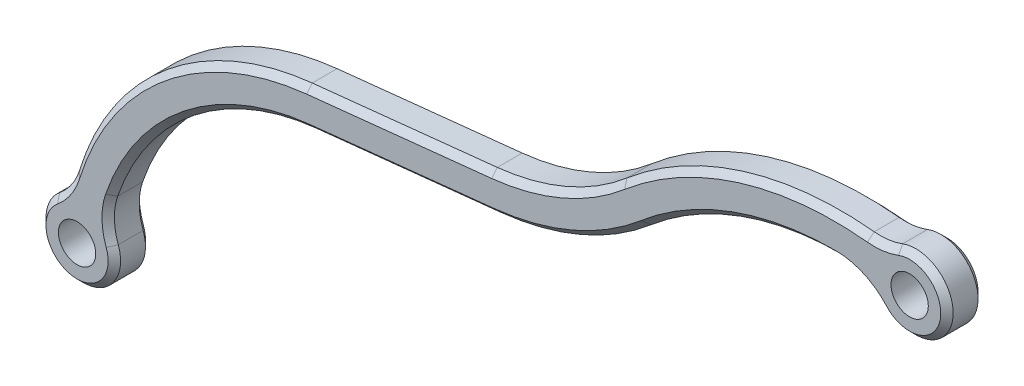
SolidWorks part; units mm, degrees
ref_plane "Спереди" through (0, 0, 0) normal (0, 0, 1) x (1, 0, 0)
ref_plane "Сверху" through (0, 0, 0) normal (0, 1, 0) x (1, 0, 0)
ref_plane "Справа" through (0, 0, 0) normal (1, 0, 0) x (0, 0, -1)
other "Configuration Table"
sketch "Sketch1" plane through (0, 0, 0) normal (0, 0, 1) x (1, 0, 0)
  line L0 (-54.4883, 1.7083) -> (-63.9363, 0.7152) construction
  line L1 (-54.4883, 1.7083) -> (-63.9363, 0.7152) construction
  line L2 (-65.383, -1.297) -> (-50.4992, 0.2674)
  circle A0 centre (-83.9505, -19.9121) radius 1.5 construction
  circle A1 centre (-83.9505, -19.9121) radius 1.5
  circle A2 centre (-17, 9.9282) radius 1.5 construction
  circle A3 centre (-17, 9.9282) radius 1.5
  circle A4 centre (-83.9505, -19.9121) radius 3
  circle A5 centre (-17, 9.9282) radius 3
  arc A6 (-12.8452, 4.492) -> (-12.8452, 1.508) centre (-13, 3) ccw construction
  arc A7 (-12.8452, 4.492) -> (-12.8452, 1.508) centre (-13, 3) ccw construction
  arc A9 (-83.3396, -17.8158) -> (-65.383, -1.297) centre (-63.2448, -21.6405) cw
  arc A10 (-50.4992, 0.2674) -> (-39.2623, 5.0886) centre (-52.6577, 20.804) ccw
  arc A11 (-39.2623, 5.0886) -> (-19.139, 10.7644) centre (-23.0284, -13.9569) cw
  dimension "D1" = 6
  dimension "D2" = 6
extrude "Boss-Extrude1" add sketch "Sketch1" along normal blind 3 contours A4 A1 | A5 A3 region at (-16.5387, 12.8066, 0) region at (-81.6367, -18.1389, 0)
sketch "Sketch2" plane through (0, 0, 0) normal (0, 0, 1) x (1, 0, 0)
  line L0 (-65.383, -1.297) -> (-50.4992, 0.2674) construction
  line L1 (-65.383, -1.297) -> (-50.4992, 0.2674)
  arc A0 (-19.139, 10.7644) -> (-39.2623, 5.0886) centre (-23.0284, -13.9569) ccw construction
  arc A1 (-50.4992, 0.2674) -> (-39.2623, 5.0886) centre (-52.6577, 20.804) ccw construction
  arc A2 (-65.383, -1.297) -> (-83.3396, -17.8158) centre (-63.2448, -21.6405) ccw construction
  arc A3 (-18.8959, 10.7249) -> (-39.2623, 5.0886) centre (-23.0284, -13.9569) ccw
  arc A4 (-50.4992, 0.2674) -> (-39.2623, 5.0886) centre (-52.6577, 20.804) ccw
  arc A5 (-65.383, -1.297) -> (-83.3396, -17.8158) centre (-63.2448, -21.6405) ccw
extrude "Extrude-Thin1" add sketch "Sketch2" along normal blind 3 thin thin type mid plane wall 3
fillet "Fillet1" radius 5 4 edges at (-84.7063, -17.0089, 1.5) (-81.8095, -17.8108, 1.5) (-19.9468, 9.3658, 1.5) (-18.9047, 12.246, 1.5)
chamfer "Chamfer1" distance 0.5 angle 45 28 edges at (-31.1067, 8.138, 0) (-43.9243, 0.4487, 0) (-57.7843, -2.0066, 0) (-75.0623, -6.8195, 0) (-30.9252, 11.3657, 0) (-81.4502, -17.1934, 0) (-45.1071, 3.2057, 0) (-84.7375, -22.8071, 0) (-58.0979, 0.977, 0) (-84.8606, -16.5059, 0) (-77.1954, -4.6867, 0) (-31.1067, 8.138, 3) (-43.9243, 0.4487, 3) (-57.7843, -2.0066, 3) (-75.0623, -6.8195, 3) (-30.9252, 11.3657, 3) (-81.4502, -17.1934, 3) (-45.1071, 3.2057, 3) (-84.7375, -22.8071, 3) (-58.0979, 0.977, 3) (-84.8606, -16.5059, 3) (-77.1954, -4.6867, 3) (-20.8969, 9.1322, 0) (-14.0837, 9.2244, 0) (-19.1882, 12.4496, 0) (-20.8969, 9.1322, 3) (-14.0837, 9.2244, 3) (-19.1882, 12.4496, 3)
